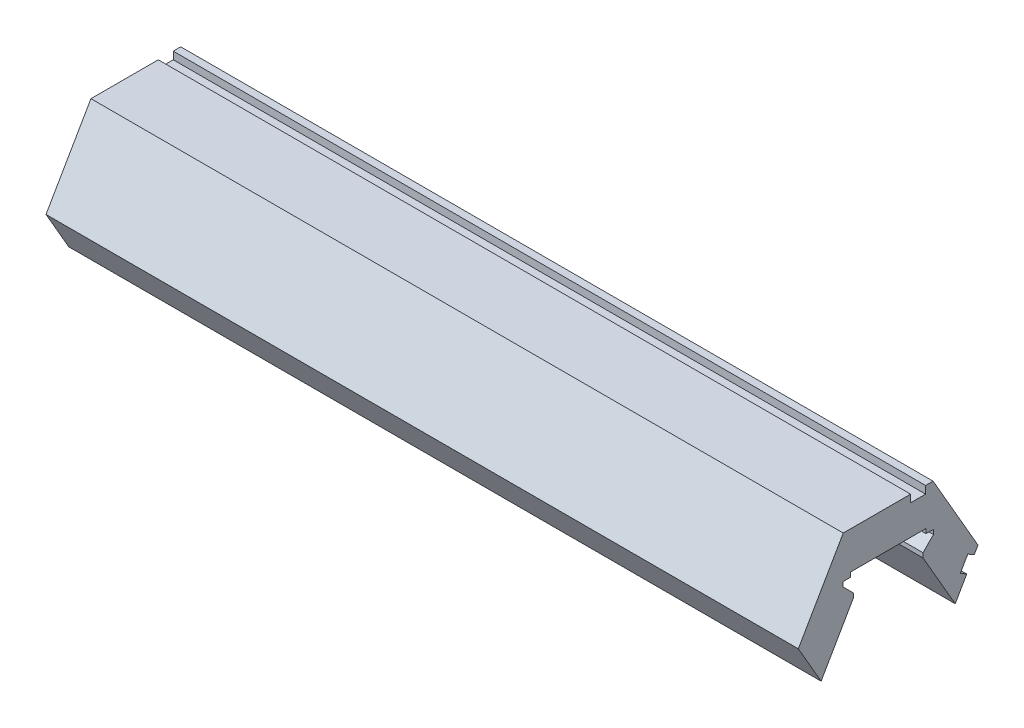
SolidWorks part; units mm, degrees
ref_plane "Front Plane" through (0, 0, 0) normal (0, 0, 1) x (1, 0, 0)
ref_plane "Top Plane" through (0, 0, 0) normal (0, 1, 0) x (1, 0, 0)
ref_plane "Right Plane" through (0, 0, 0) normal (1, 0, 0) x (0, 0, -1)
sketch "Master Design Profile" plane through (0, 0, 0) normal (1, 0, 0) x (0, 0, -1)
  line L0 (-5.05, 5.3923) -> (5.05, 5.3923)
  line L1 (12, 0) -> (6, 10.3923)
  line L2 (6, 10.3923) -> (-6, 10.3923)
  line L3 (-6, 10.3923) -> (-12, 0)
  line L4 (-12, 0) -> (-8.9579, -5.2691)
  line L5 (0, -10.3923) -> (6, -10.3923) construction
  line L6 (8.9579, -5.2691) -> (12, 0)
  line L7 (-5.05, 5.3923) -> (-5.05, 4.7923)
  line L8 (-5.05, 4.7923) -> (-6.05, 4.7923)
  line L9 (0, -28.6883) -> (0, 28.6883) construction
  line L10 (-6.05, 4.7923) -> (-6.05, 4.1923)
  line L11 (-6.05, 4.1923) -> (-4.65, 2.7923)
  line L13 (-4.65, 2.7923) -> (-4.65, 2.1923)
  line L14 (-4.65, 2.1923) -> (-8.9579, -5.2691)
  line L15 (4.65, 2.1923) -> (8.9579, -5.2691)
  line L16 (4.65, 2.7923) -> (4.65, 2.1923)
  line L17 (6.05, 4.1923) -> (4.65, 2.7923)
  line L18 (6.05, 4.7923) -> (6.05, 4.1923)
  line L19 (5.05, 4.7923) -> (6.05, 4.7923)
  line L20 (5.05, 5.3923) -> (5.05, 4.7923)
  line L21 (-9, -5.1962) -> (-6, -10.3923) construction
  line L22 (-8.9579, -5.2691) -> (-9, -5.1962) construction
  line L23 (-6, -10.3923) -> (0, -10.3923) construction
  line L24 (6, -10.3923) -> (9, -5.1962) construction
  line L25 (9, -5.1962) -> (8.9579, -5.2691) construction
  circle A0 centre (0, 0) radius 10.3923 construction
  point P15 (0, 0)
  point P16 (0, 5.3923)
  dimension "D1" = 10.1
  dimension "D2" = 0.6
  dimension "D3" = 0.6
  dimension "D4" = 1
  dimension "D5" = 135
  dimension "D6" = 2
  dimension "D7" = 5
  dimension "D8" = 210
  dimension "D9" = 0.6
  dimension "D10" = 12
sketch "LED Groove Profile Test" plane through (0, 0, 0) normal (1, 0, 0) x (0, 0, -1)
  line L0 (4.65, 2.7923) -> (4.65, 2.1923) construction
  line L1 (6.05, 4.1923) -> (4.65, 2.7923) construction
  line L2 (6.05, 4.7923) -> (6.05, 4.1923) construction
  line L3 (5.05, 4.7923) -> (6.05, 4.7923) construction
  line L4 (5.05, 5.3923) -> (5.05, 4.7923) construction
  line L5 (-5.05, 5.3923) -> (5.05, 5.3923) construction
  line L6 (-5.05, 5.3923) -> (-5.05, 4.7923) construction
  line L7 (-5.05, 4.7923) -> (-6.05, 4.7923) construction
  line L8 (-6.05, 4.7923) -> (-6.05, 4.1923) construction
  line L9 (-6.05, 4.1923) -> (-4.65, 2.7923) construction
  line L10 (-4.65, 2.7923) -> (-4.65, 2.1923) construction
  line L11 (-4.65, 2.7923) -> (-4.65, 2.1923)
  line L12 (-6.05, 4.1923) -> (-4.65, 2.7923)
  line L13 (-6.05, 4.7923) -> (-6.05, 4.1923)
  line L14 (-5.05, 4.7923) -> (-6.05, 4.7923)
  line L15 (-5.05, 5.3923) -> (-5.05, 4.7923)
  line L16 (-5.05, 5.3923) -> (5.05, 5.3923)
  line L17 (5.05, 5.3923) -> (5.05, 4.7923)
  line L18 (5.05, 4.7923) -> (6.05, 4.7923)
  line L19 (6.05, 4.7923) -> (6.05, 4.1923)
  line L20 (6.05, 4.1923) -> (4.65, 2.7923)
  line L21 (4.65, 2.7923) -> (4.65, 2.1923)
  line L22 (-4.65, 2.1923) -> (-7.5, 2.1923)
  line L23 (-7.5, 2.1923) -> (-7.5, 7.1923)
  line L24 (-7.5, 7.1923) -> (7.5, 7.1923)
  line L25 (7.5, 7.1923) -> (7.5, 2.1923)
  line L26 (7.5, 2.1923) -> (4.65, 2.1923)
  line L27 (0, -28.6883) -> (0, 28.6883) construction
  point P0 (0, 7.1923)
  dimension "D1" = 5
  dimension "D2" = 15
extrude "Boss-Extrude1" [suppressed] add sketch "LED Groove Profile Test" along normal mid plane 15
sketch "LED Segment" plane through (0, 0, 0) normal (1, 0, 0) x (0, 0, -1)
  line L0 (8.9579, -5.2691) -> (12, 0) construction
  line L1 (12, 0) -> (6, 10.3923) construction
  line L2 (6, 10.3923) -> (-6, 10.3923) construction
  line L3 (-6, 10.3923) -> (-12, 0) construction
  line L4 (-12, 0) -> (-8.9579, -5.2691) construction
  line L5 (-4.65, 2.1923) -> (-8.9579, -5.2691) construction
  line L6 (4.65, 2.1923) -> (8.9579, -5.2691) construction
  line L7 (4.65, 2.7923) -> (4.65, 2.1923) construction
  line L8 (6.05, 4.1923) -> (4.65, 2.7923) construction
  line L9 (6.05, 4.7923) -> (6.05, 4.1923) construction
  line L10 (5.05, 4.7923) -> (6.05, 4.7923) construction
  line L11 (5.05, 5.3923) -> (5.05, 4.7923) construction
  line L12 (-5.05, 5.3923) -> (5.05, 5.3923) construction
  line L13 (-5.05, 5.3923) -> (-5.05, 4.7923) construction
  line L14 (-5.05, 4.7923) -> (-6.05, 4.7923) construction
  line L15 (-6.05, 4.7923) -> (-6.05, 4.1923) construction
  line L16 (-4.65, 2.7923) -> (-4.65, 2.1923) construction
  line L17 (-6.05, 4.1923) -> (-4.65, 2.7923) construction
  line L18 (8.9579, -5.2691) -> (12, 0)
  line L19 (12, 0) -> (6, 10.3923)
  line L20 (6, 10.3923) -> (-6, 10.3923)
  line L21 (-6, 10.3923) -> (-12, 0)
  line L22 (-12, 0) -> (-8.9579, -5.2691)
  line L23 (-4.65, 2.1923) -> (-8.9579, -5.2691)
  line L24 (4.65, 2.1923) -> (8.9579, -5.2691)
  line L25 (4.65, 2.7923) -> (4.65, 2.1923)
  line L26 (6.05, 4.1923) -> (4.65, 2.7923)
  line L27 (6.05, 4.7923) -> (6.05, 4.1923)
  line L28 (5.05, 4.7923) -> (6.05, 4.7923)
  line L29 (5.05, 5.3923) -> (5.05, 4.7923)
  line L30 (-5.05, 5.3923) -> (5.05, 5.3923)
  line L31 (-5.05, 5.3923) -> (-5.05, 4.7923)
  line L32 (-5.05, 4.7923) -> (-6.05, 4.7923)
  line L33 (-6.05, 4.7923) -> (-6.05, 4.1923)
  line L34 (-4.65, 2.7923) -> (-4.65, 2.1923)
  line L35 (-6.05, 4.1923) -> (-4.65, 2.7923)
extrude "Boss-Extrude2" add sketch "LED Segment" along normal mid plane 100.5
sketch "Sketch3" plane through (50.25, 0, 0) normal (1, 0, 0) x (0, 0, -1)
  line L5 (5, 10.3923) -> (5, 9.3923)
  line L11 (6, 10.3923) -> (-6, 10.3923) construction
  line L12 (5, 9.3923) -> (3, 9.3923)
  line L13 (3, 9.3923) -> (3, 10.3923)
  line L14 (3, 10.3923) -> (5, 10.3923)
  line L15 (12, 0) -> (6, 10.3923) construction
  line L16 (12, 0) -> (6, 10.3923) construction
  line L17 (11.6944, 6.7518) -> (6.3056, 3.6405) construction
  line L18 (10.5, -2.5981) -> (11.5, -0.866)
  line L19 (9.634, -2.0981) -> (10.5, -2.5981)
  line L20 (10.634, -0.366) -> (9.634, -2.0981)
  line L21 (11.5, -0.866) -> (10.634, -0.366)
  point P12 (9, 5.1962)
  dimension "D1" = 1
  dimension "D2" = 1
  dimension "D3" = 2
extrude "Cut-Extrude2" cut sketch "Sketch3" against normal through all
